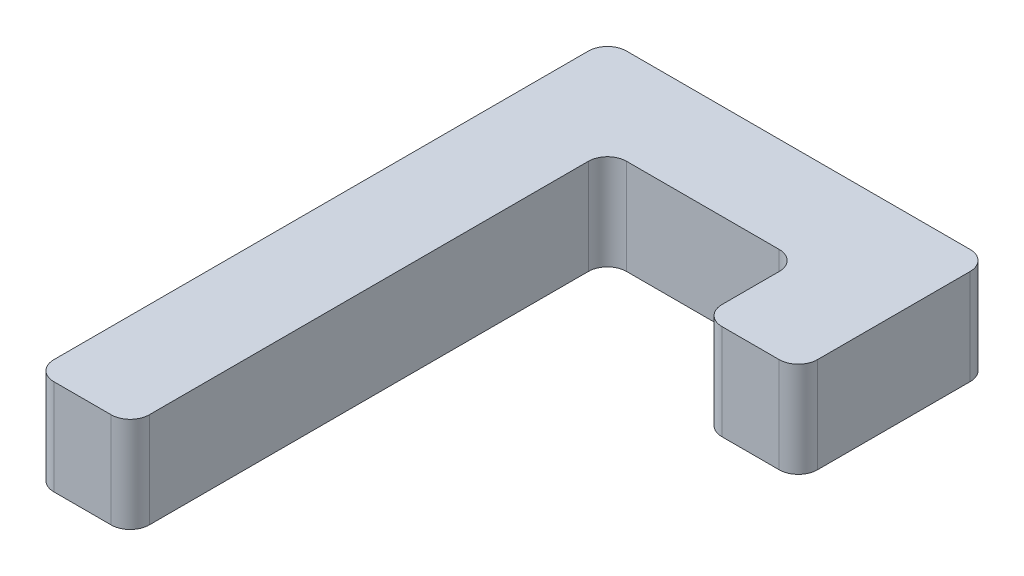
SolidWorks part; units mm, degrees
ref_plane "Front Plane" through (0, 0, 0) normal (0, 0, 1) x (1, 0, 0)
ref_plane "Top Plane" through (0, 0, 0) normal (0, 1, 0) x (1, 0, 0)
ref_plane "Right Plane" through (0, 0, 0) normal (1, 0, 0) x (0, 0, -1)
sketch "Sketch1" plane through (0, 0, 0) normal (0, 1, 0) x (1, 0, 0)
  line L0 (0, 0) -> (0, 76.2)
  line L1 (0, 76.2) -> (50.8, 76.2)
  line L2 (50.8, 76.2) -> (50.8, 50.8)
  line L3 (50.8, 50.8) -> (38.1, 50.8)
  line L4 (38.1, 50.8) -> (38.1, 63.5)
  line L5 (38.1, 63.5) -> (12.7, 63.5)
  line L6 (12.7, 63.5) -> (12.7, 0)
  line L7 (12.7, 0) -> (0, 0)
  dimension "D1" = 25.4
  dimension "D2" = 50.8
  dimension "D3" = 12.7
  dimension "D4" = 12.7
  dimension "D5" = 25.4
  dimension "D6" = 76.2
extrude "Boss-Extrude1" add sketch "Sketch1" along normal blind 12.7
fillet "Fillet1" radius 2.54 8 edges at (50.8, 6.35, -76.2) (38.1, 6.35, -63.5) (50.8, 6.35, -50.8) (38.1, 6.35, -50.8) (12.7, 6.35, 0) (0, 6.35, 0) (12.7, 6.35, -63.5) (0, 6.35, -76.2)
ref_plane "Plane1" through (25.4, 0, 0) normal (1, 0, 0) x (0, 0, -1)
